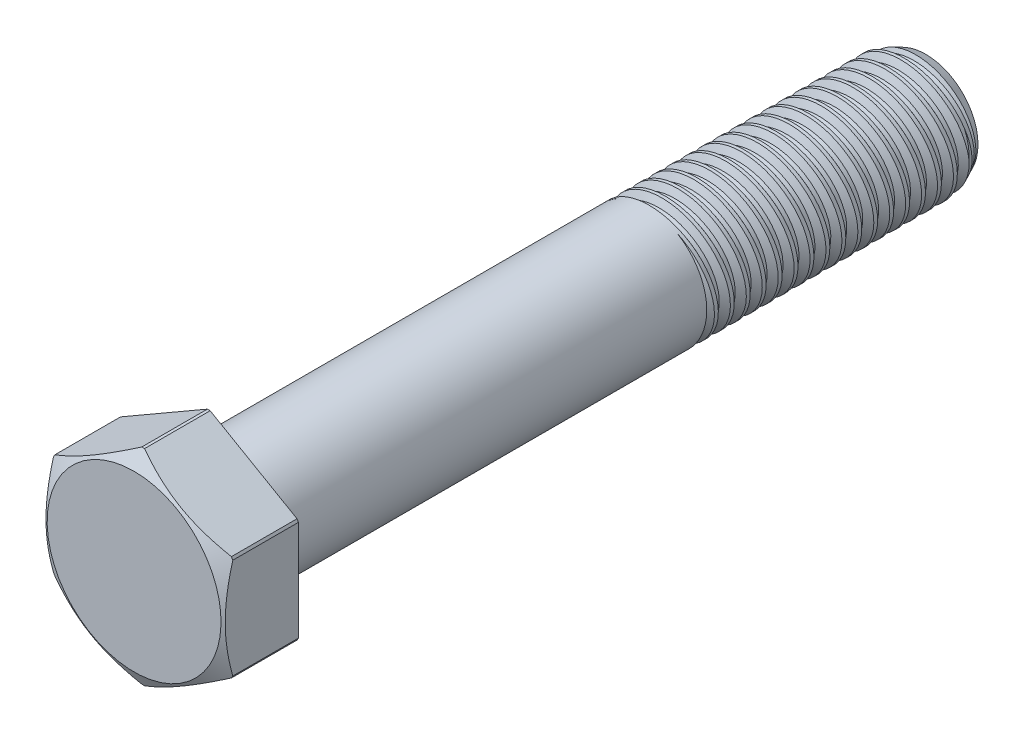
SolidWorks part; units mm, degrees
ref_plane "Front" through (0, 0, 0) normal (0, 0, 1) x (1, 0, 0)
ref_plane "Top" through (0, 0, 0) normal (0, 1, 0) x (1, 0, 0)
ref_plane "Right" through (0, 0, 0) normal (1, 0, 0) x (0, 0, -1)
sketch "Sketch1" plane through (0, 0, 0) normal (1, 0, 0) x (0, 0, -1)
  line L0 (0, 0) -> (-69.85, 0) construction
  line L1 (-69.85, 0) -> (-69.85, 14.2875) construction
  line L2 (-69.85, 0) -> (-81.7563, 0) construction
  line L3 (0, -9.525) -> (44.45, -9.525) construction
  line L4 (0, 0) -> (44.45, 0)
  line L5 (0, 0) -> (0, 9.525)
  line L6 (0, 9.525) -> (44.45, 9.525)
  line L7 (44.45, 0) -> (44.45, 9.525)
  dimension "Screw Dia" = 19.05
  dimension "Min Thread Length" = 44.45
  dimension "Screw Length" = 114.3
  dimension "Head Height" = 11.9062
  dimension "Head Width" = 28.575
revolve "Revolve1" add sketch "Sketch1" angle 360 about L0
sketch "Sketch2" plane through (0, 0, 0) normal (1, 0, 0) x (0, 0, -1)
  line L0 (0, 9.525) -> (0, -9.525) construction
  line L1 (0, -9.525) -> (2.54, -9.525) construction
  line L2 (2.54, -9.525) -> (0, 9.525) construction
  line L3 (0, 9.525) -> (0.3147, 9.567) construction
  line L4 (2.5177, 9.8607) -> (0.3147, 9.567)
  line L5 (0.3147, 9.567) -> (1.2832, 8.3091)
  line L6 (1.2832, 8.3091) -> (1.9126, 8.393)
  line L7 (1.9126, 8.393) -> (2.5177, 9.8607)
  line L8 (1.5979, 8.3511) -> (1.4162, 9.7138) construction
  line L9 (0, 0) -> (0, 9.525) construction
  line L10 (0, 9.525) -> (1.4414, 9.525) construction
  line L11 (1.4414, 9.525) -> (3.9814, -9.525) construction
  line L12 (3.9814, -9.525) -> (2.54, -9.525) construction
  line L13 (0, -9.525) -> (44.45, -9.525) construction
  line L14 (0, -0.3615) -> (5.4228, 0.3615) construction
  line L15 (0, 9.525) -> (44.45, 9.525) construction
  point P17 (2.7114, 0)
  dimension "D1" = 2.54
  dimension "Thread Pitch" = 2.54
  dimension "D3" = 0.635
  dimension "D4" = 0.3175
  dimension "D5" = 60
revolve "Cut-Revolve1" cut sketch "Sketch2" angle 360 about L14
sketch "Sketch3" plane through (0, 0, 0) normal (1, 0, 0) x (0, 0, -1)
  line L0 (41.8425, 9.525) -> (44.45, 8.3091)
  line L1 (44.45, 8.3091) -> (44.45, 9.525)
  line L2 (44.45, 9.525) -> (41.8425, 9.525)
  line L3 (0, 9.525) -> (44.45, 9.525) construction
  line L4 (44.45, 0) -> (44.45, 9.525) construction
  line L5 (1.2832, 8.3091) -> (44.45, 8.3091) construction
  line L6 (41.8425, 9.525) -> (41.8425, -9.525) construction
  line L7 (0, -9.525) -> (44.45, -9.525) construction
  line L8 (0, 0) -> (41.8425, 0) construction
  dimension "D1" = 25
  dimension "D2" = 19.05
revolve "Cut-Revolve2" cut sketch "Sketch3" angle 360 about L8
pattern_linear "LPattern1" count 2 spacing 2.54 along (0, 0, 1) count 18 spacing 2.54 along (0, 0, 1)
sketch "Sketch4" plane through (0, 0, 0) normal (1, 0, 0) x (0, 0, -1)
  line L0 (-69.85, 0) -> (-69.85, 14.2875) construction
  line L1 (0, 0) -> (-69.85, 0)
  line L2 (0, 0) -> (0, 9.525)
  line L3 (0, 9.525) -> (-69.85, 9.525)
  line L4 (-69.85, 0) -> (-69.85, 9.525)
  line L5 (0, 9.525) -> (44.45, 9.525) construction
  line L6 (-69.85, 0) -> (-81.7563, 0) construction
revolve "Revolve2" add sketch "Sketch4" angle 360 about L6
sketch "Sketch5" plane through (0, 0, 69.85) normal (0, 0, 1) x (1, 0, 0)
  line L1 (0, 16.4978) -> (-14.2875, 8.2489)
  line L2 (-14.2875, 8.2489) -> (-14.2875, -8.2489)
  line L3 (-14.2875, -8.2489) -> (0, -16.4978)
  line L4 (0, -16.4978) -> (14.2875, -8.2489)
  line L5 (14.2875, -8.2489) -> (14.2875, 8.2489)
  line L6 (14.2875, 8.2489) -> (0, 16.4978)
  circle A0 centre (0, 0) radius 14.2875 construction
  dimension "D1" = 28.575
extrude "Extrude1" add sketch "Sketch5" along normal up to vertex
sketch "Sketch6" plane through (0, 0, 0) normal (1, 0, 0) x (0, 0, -1)
  line L0 (-81.7563, 13.8589) -> (-80.306, 16.3708)
  line L1 (-80.306, 16.3708) -> (-69.85, 16.3708)
  line L2 (-69.85, 16.3708) -> (-69.85, 16.8788)
  line L3 (-69.85, 16.8788) -> (-81.7562, 16.8788)
  line L4 (-81.7562, 16.8788) -> (-81.7563, 13.8589)
  line L5 (-81.7563, 8.2489) -> (-81.7563, 16.4978) construction
  line L6 (-81.7563, 16.4978) -> (-69.85, 16.4978) construction
  line L7 (-69.85, 8.2489) -> (-69.85, 16.4978) construction
  line L8 (0, 0) -> (-80.306, 0) construction
  line L9 (-69.85, 0) -> (-81.7563, 0) construction
  line L10 (-80.306, 0) -> (-80.306, 16.3708) construction
  line L11 (-75.8031, 16.8788) -> (-75.8031, 0) construction
  dimension "D1" = 30
  dimension "D2" = 0.127
  dimension "D3" = 0.508
  dimension "D4" = 27.7177
  dimension "D5" = 11.9063
  dimension "D6" = 114.3
revolve "Cut-Revolve3" cut sketch "Sketch6" angle 360 about L8
fillet "Fillet1" radius 1.905
equation "\"D3@Sketch2\"=\"Thread Pitch@Sketch2\"/4"
equation "\"D4@Sketch2\"=\"Thread Pitch@Sketch2\"/8"
equation "\"D1@Sketch2\"=\"Thread Pitch@Sketch2\""
equation "\"D3@LPattern1\"=\"Thread Pitch@Sketch2\""
equation "\"D4@LPattern1\"=\"Thread Pitch@Sketch2\""
equation "\"D2@LPattern1\"=\"Min Thread Length@Sketch1\"/\"Thread Pitch@Sketch2\""
equation "\"D4@Sketch6\"=\"Head Width@Sketch1\"*.97"
equation "\"D1@Fillet1\"=\"Screw Dia@Sketch1\"/10"
